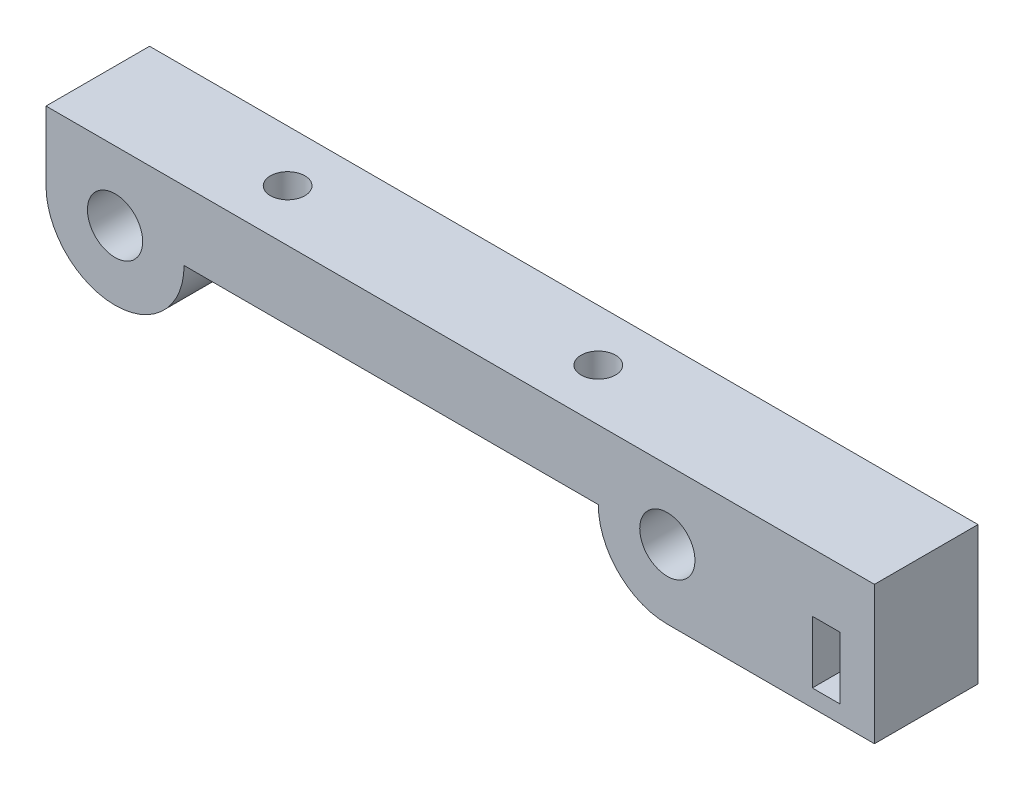
SolidWorks part; units mm, degrees
material "ABS"
ref_plane "Plano frontal" through (0, 0, 0) normal (0, 0, 1) x (1, 0, 0)
ref_plane "Plano superior" through (0, 0, 0) normal (0, 1, 0) x (1, 0, 0)
ref_plane "Plano direito" through (0, 0, 0) normal (1, 0, 0) x (0, 0, -1)
sketch "Esboço1" plane through (0, 0, 0) normal (0, 0, 1) x (1, 0, 0)
  line L0 (0, 0) -> (0, -10) construction
  line L1 (50, 0) -> (70, 0)
  line L2 (-50, -10) -> (-50, 0)
  line L3 (-50, 0) -> (50, 0)
  line L5 (70, 0) -> (70, -20)
  line L6 (70, -20) -> (40, -20)
  line L7 (-30, -10) -> (30, -10)
  line L9 (65, -17.5) -> (61, -17.5)
  line L10 (65, -17.5) -> (65, -8.5)
  line L11 (65, -8.5) -> (61, -8.5)
  line L12 (61, -17.5) -> (61, -8.5)
  line L13 (65, -17.5) -> (61, -8.5) construction
  line L14 (65, -8.5) -> (61, -17.5) construction
  circle A0 centre (-40, -10) radius 4
  circle A1 centre (40, -10) radius 4
  arc A2 (-50, -10) -> (-30, -10) centre (-40, -10) ccw
  arc A3 (40, -20) -> (30, -10) centre (40, -10) cw
  point P0 (0, 0)
  point P13 (63, -13)
  point P22 (0, 0)
  dimension "D3" = 8
  dimension "D4" = 80
  dimension "D2" = 10
  dimension "D1" = 100
  dimension "D5" = 20
  dimension "D6" = 7
  dimension "D7" = 9
  dimension "D8" = 4
  dimension "D9" = 7
extrude "Ressalto-extrusão1" add sketch "Esboço1" along normal blind 15
sketch "Esboço2" plane through (0, -10, 0) normal (0, -1, 0) x (1, 0, 0)
  line L0 (0, 0) -> (0, 15) construction
  line L1 (-30, 0) -> (30, 0) construction
  line L2 (-30, 15) -> (30, 15) construction
  circle A0 centre (-22.5, 7.5) radius 2.5
  circle A1 centre (22.5, 7.5) radius 2.5
  point P10 (0, 0)
  point P11 (0, 7.5)
  dimension "D2" = 5
  dimension "D1" = 45
extrude "Corte-extrusão1" cut sketch "Esboço2" against normal blind 15 contours A1 | A0 region at (22.5, -10, 7.5)
